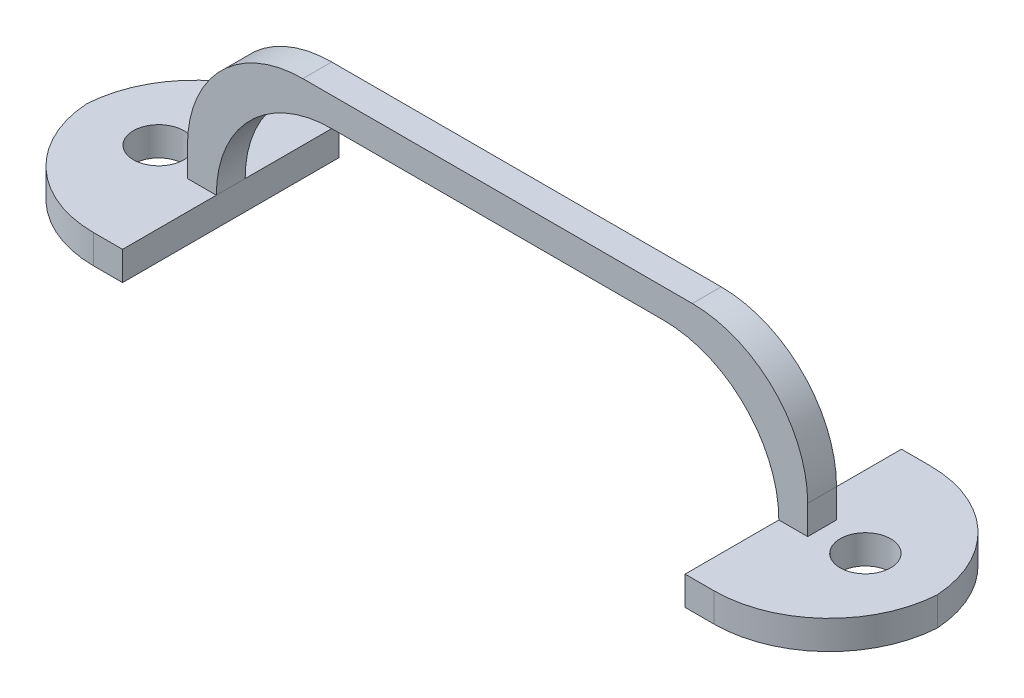
SolidWorks part; units mm, degrees
ref_plane "前视基准面" through (0, 0, 0) normal (0, 0, 1) x (1, 0, 0)
ref_plane "上视基准面" through (0, 0, 0) normal (0, 1, 0) x (1, 0, 0)
ref_plane "右视基准面" through (0, 0, 0) normal (1, 0, 0) x (0, 0, -1)
other "Configuration Table"
sketch "Sketch3" plane through (0, 0, 0) normal (0, 1, 0) x (1, 0, 0)
  line L1 (-22.6095, -1.173) -> (-12.6095, -1.173)
  line L2 (-22.6095, -1.173) -> (-22.6095, -16.173)
  line L3 (-22.6095, -16.173) -> (-12.6095, -16.173)
  line L4 (-12.6095, -1.173) -> (-12.6095, -16.173)
  line L5 (26.3905, -1.173) -> (36.3905, -1.173)
  line L6 (26.3905, -1.173) -> (26.3905, -16.173)
  line L7 (26.3905, -16.173) -> (36.3905, -16.173)
  line L8 (36.3905, -1.173) -> (36.3905, -16.173)
  circle A0 centre (-17.6095, -8.673) radius 1.75
  circle A1 centre (31.3905, -8.673) radius 1.75
  point P11 (-17.6095, -1.173)
  point P12 (31.3905, -1.173)
  point P13 (36.3905, -8.673)
  point P14 (-12.6095, -8.673)
  dimension "D3" = 3.5
  dimension "D4" = 3.5
  dimension "D1" = 10
  dimension "D2" = 15
  dimension "D5" = 49
extrude "Boss-Extrude1" add sketch "Sketch3" along normal blind 2 contours L2 L1 L4 L3 | L6 L5 L8 L7 | A0 | A1
ref_plane "Plane1" through (0, 0, 8.673) normal (0, 0, 1) x (1, 0, 0)
sketch "Sketch4" plane through (0, 0, 8.673) normal (0, 0, 1) x (1, 0, 0)
  line L0 (-12.6095, 2) -> (-12.6095, 10)
  line L1 (-22.6095, 2) -> (-12.6095, 2) construction
  line L2 (-12.6095, 2) -> (-12.6095, 0) construction
  line L3 (-12.6095, 10) -> (26.3905, 10)
  line L4 (26.3905, 10) -> (26.3905, 2)
  line L5 (26.3905, 2) -> (28.3905, 2)
  line L6 (26.3905, 2) -> (36.3905, 2) construction
  line L7 (28.3905, 2) -> (28.3905, 12)
  line L8 (28.3905, 12) -> (-14.6095, 12)
  line L9 (-14.6095, 12) -> (-14.6095, 2)
  line L10 (-12.6095, 2) -> (-14.6095, 2)
  dimension "D1" = 2
  dimension "D2" = 2
  dimension "D3" = 10
  dimension "D4" = 2
extrude "Boss-Extrude2" add sketch "Sketch4" along normal blind 1 and the other way blind 1
fillet "Fillet1" radius 8 8 edges at (-22.6095, 1, 1.173) (-22.6095, 1, 16.173) (36.3905, 1, 1.173) (36.3905, 1, 16.173) (28.3905, 12, 8.673) (26.3905, 10, 8.673) (-14.6095, 12, 8.673) (-12.6095, 10, 8.673)
